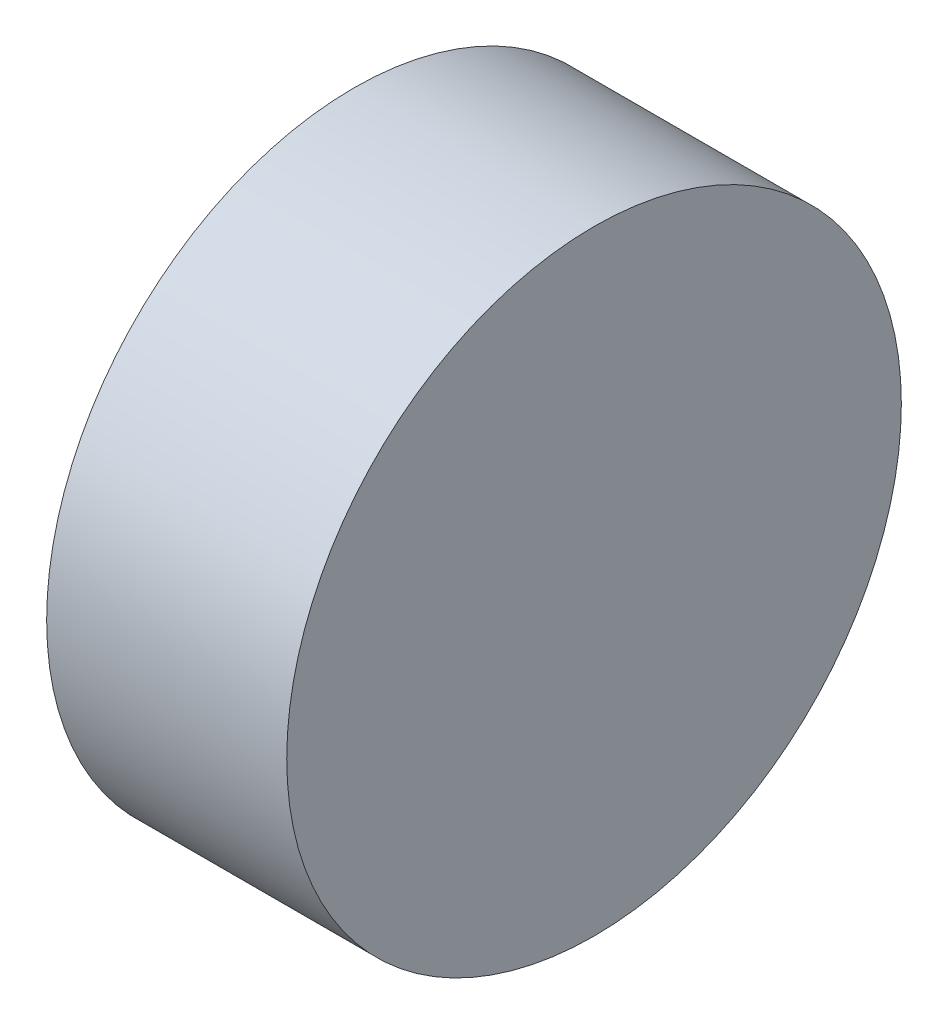
SolidWorks part; units mm, degrees
ref_plane "Front Plane" through (0, 0, 0) normal (0, 0, 1) x (1, 0, 0)
ref_plane "Top Plane" through (0, 0, 0) normal (0, 1, 0) x (1, 0, 0)
ref_plane "Right Plane" through (0, 0, 0) normal (1, 0, 0) x (0, 0, -1)
sketch "Sketch1" plane through (0, 0, 0) normal (1, 0, 0) x (0, 0, -1)
  circle A0 centre (0, 0) radius 32
  dimension "D1" = 64
extrude "Boss-Extrude1" add sketch "Sketch1" along normal blind 12.5 and the other way blind 12.5
